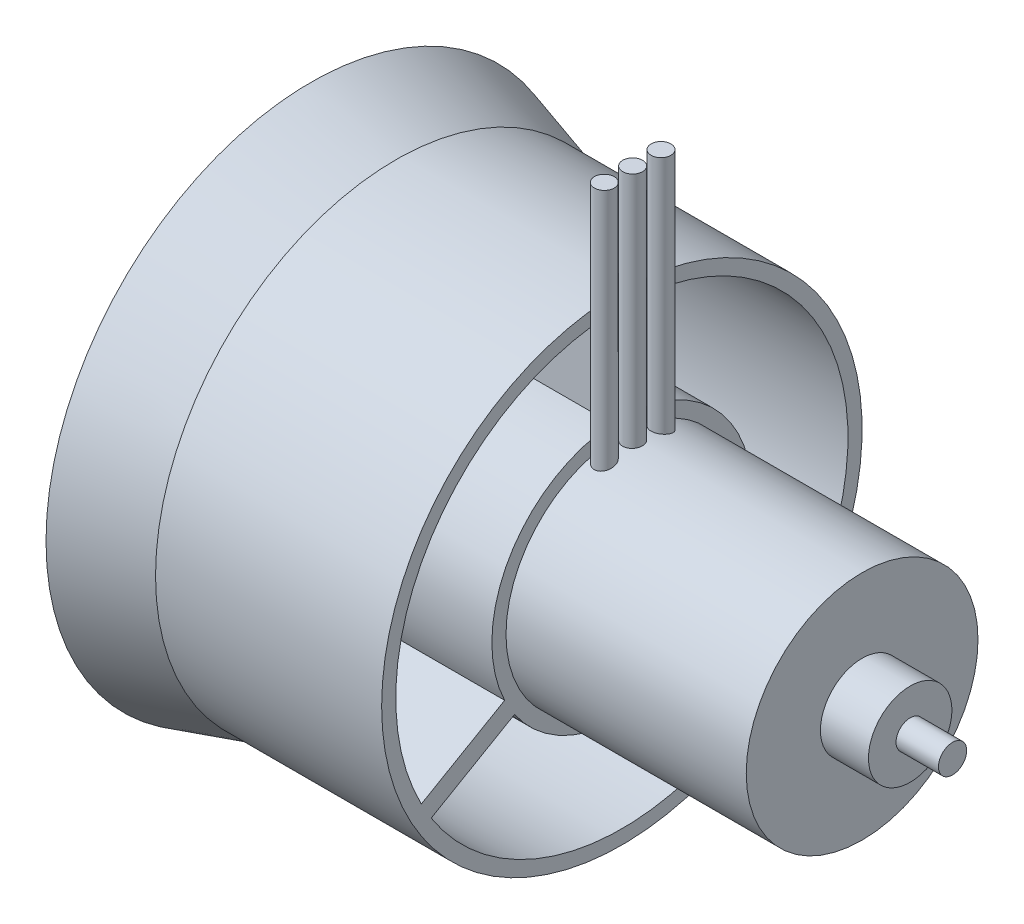
SolidWorks part; units mm, degrees
ref_plane "Plan de face" through (0, 0, 0) normal (0, 0, 1) x (1, 0, 0)
ref_plane "Plan de dessus" through (0, 0, 0) normal (0, 1, 0) x (1, 0, 0)
ref_plane "Plan de droite" through (0, 0, 0) normal (1, 0, 0) x (0, 0, -1)
sketch "Esquisse1" plane through (0, 0, 0) normal (0, 0, 1) x (1, 0, 0)
  line L0 (17.2215, 7.9823) -> (67.2215, 7.9823) construction
  line L1 (0, 0) -> (50, 0)
  line L3 (50, 1) -> (47, 1)
  line L4 (47, 1) -> (47, 2.95)
  line L5 (47, 2.95) -> (43.6, 2.95)
  line L6 (43.6, 2.95) -> (43.6, 8.2)
  line L7 (43.6, 8.2) -> (26.6, 8.2)
  line L8 (26.6, 8.2) -> (26.6, 17)
  line L9 (26.6, 17) -> (10.6, 17)
  line L10 (10.6, 17) -> (4.6, 18.75)
  line L11 (4.6, 18.75) -> (4.6, 5.75)
  line L12 (4.6, 5.75) -> (0, 3.3705)
  line L24 (50, 1) -> (50, 0)
  line L25 (0, 0) -> (0, 3.3705)
  dimension "D1" = 50
  dimension "D2" = 22
  dimension "D3" = 34
  dimension "D4" = 37.5
  dimension "D5" = 5.75
  dimension "D6" = 4.6
  dimension "D7" = 6
  dimension "D8" = 8.2
  dimension "D9" = 17
  dimension "D10" = 3.4
  dimension "D11" = 2.95
  dimension "D12" = 1
revolve "Révolution1" add sketch "Esquisse1" angle 360 about L1
ref_axis "Axe1" through (45.2072, 0, 0) along (-1, 0, 0)
sketch "Esquisse4" plane through (26.6, 0, 0) normal (1, 0, 0) x (0, 0, -1)
  line L0 (0, 0) -> (-14.7224, -8.5) construction
  line L3 (0, 0) -> (0, 17) construction
  line L4 (-0.7, 15.9847) -> (-0.7, 9.1733)
  line L5 (-14.1931, -7.3861) -> (-8.2943, -3.9804)
  circle A6 centre (0, 0) radius 17 construction
  circle A7 centre (0, 0) radius 17 construction
  circle A10 centre (0, 0) radius 16
  arc A11 (-0.7, 15.9847) -> (-14.1931, -7.3861) centre (0, 0) ccw
  circle A13 centre (0, 0) radius 9.2
  arc A14 (-0.7, 9.1733) -> (-8.2943, -3.9804) centre (0, 0) ccw
  dimension "D1" = 120
  dimension "D4" = 0.7
  dimension "D5" = 0.7
extrude "Enlèv. mat.-Extru.1" cut sketch "Esquisse4" against normal through all
pattern_circular "Répétition circulaire1" count 3 over 360 about axis through (45.2072, 0, 0) along (-1, 0, 0) of "Enlèv. mat.-Extru.1"
sketch "Esquisse5" plane through (0, 0, 0) normal (0, 1, 0) x (1, 0, 0)
  line L0 (45.2072, 0) -> (0.2177, 0) construction
  line L1 (-20.625, 0) -> (20.625, 0) construction
  circle A0 centre (27.3614, 0) radius 0.7
  circle A1 centre (27.3614, 2.0072) radius 0.7
  circle A2 centre (27.3614, -2.0072) radius 0.7
  dimension "D1" = 1.4
extrude "Boss.-Extru.1" add sketch "Esquisse5" along normal blind 25
equation "\"D5@Esquisse4\"=\"D4@Esquisse4\""
equation "\"D8@Esquisse1\"=16.4/2"
